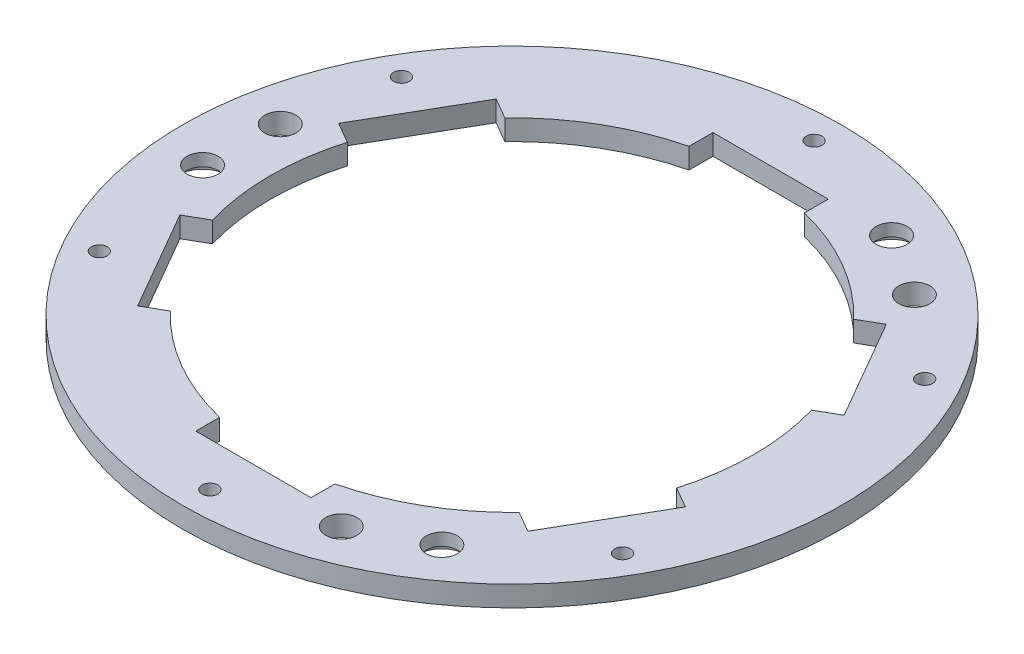
SolidWorks part; units mm, degrees
material "6061 Alloy"
ref_plane "Front Plane" through (0, 0, 0) normal (0, 0, 1) x (1, 0, 0)
ref_plane "Top Plane" through (0, 0, 0) normal (0, 1, 0) x (1, 0, 0)
ref_plane "Right Plane" through (0, 0, 0) normal (1, 0, 0) x (0, 0, -1)
sketch "Sketch1" plane through (0, 0, 0) normal (0, 1, 0) x (1, 0, 0)
  line L0 (-13.335, -54.2656) -> (-13.335, -58.1814)
  line L1 (13.335, -54.2656) -> (13.335, -58.1814)
  line L2 (-13.335, -59.7901) -> (13.335, -59.7901)
  line L3 (13.335, -58.1814) -> (13.335, -59.7901)
  line L4 (-13.335, -58.1814) -> (-13.335, -59.7901)
  line L5 (0, 0) -> (-65.7887, -5.7558) construction
  line L6 (0, 0) -> (0, -23.1086) construction
  line L7 (0, 0) -> (17.8146, -65.9496) construction
  line L8 (0, 0) -> (27.4515, -55.5868) construction
  line L9 (-65.0367, 11.4677) -> (0, 0) construction
  circle A0 centre (0, 0) radius 55.88
  circle A1 centre (0, 0) radius 76.2
  circle A2 centre (0, 0) radius 59.69
  circle A3 centre (0, -69.85) radius 1.8288
  circle A4 centre (-65.7887, -5.7558) radius 3.5941
  circle A5 centre (-65.0367, 11.4677) radius 3.5941
  circle A6 centre (42.4497, 50.5896) radius 3.5941
  circle A7 centre (22.587, -62.0573) radius 3.5941
  point P24 (0, 0)
  point P29 (0, 0)
  dimension "D1" = 111.76
  dimension "D2" = 152.4
  dimension "D8" = 3.6576
  dimension "D11" = 7.1882
  dimension "D4" = 13.335
  dimension "D5" = 13.335
  dimension "D7" = 69.85
  dimension "D6" = 5.5245
  dimension "D9" = 66.04
  dimension "D10" = 85
  dimension "D13" = 17.8146
  dimension "D14" = 68.3133
  dimension "D16" = 61.9958
  dimension "D17" = 14.1512
  dimension "D15" = 15
  dimension "D3" = 3.81
  dimension "D12" = 2
  dimension "D18" = 3
extrude "Boss-Extrude1" add sketch "Sketch1" along normal blind 4.7625 contours L1 A2 L0 A0 | A1 A2 A0 region at (-15.0127, 0, 56.2235) region at (-74.0447, 0, 0)
pattern_circular "CirPattern1" count 6 over 360 about axis through (0, 4.7625, 0) along (0, 1, 0) of face at (-13.335, 2.3813, 57.0278) of face at (13.335, 2.3813, 57.0278) of face at (0, 4.7625, 71.6788) of face at (0, 2.3813, 59.7901)
sketch "Sketch2" plane through (0, 0, 0) normal (1, 0, 0) x (0, 0, -1)
  line L0 (76.2, 4.7625) -> (-76.2, 4.7625) construction
  line L1 (-76.2, 0) -> (76.2, 0) construction
  line L2 (76.2, 4.7625) -> (-76.2, 4.7625)
  line L3 (-76.2, 0) -> (76.2, 0)
  line L4 (0, 0) -> (0, 4.7625) construction
  circle A0 centre (-75.2856, 0) radius 2.667
  dimension "D1" = 5.334
  dimension "D2" = 0.9144
revolve "Cut-Revolve1" [suppressed] cut sketch "Sketch2" angle 360 about L4
sketch "Sketch4" plane through (0, 0, 0) normal (0, -1, 0) x (1, 0, 0)
  line L0 (0, 0) -> (-65.7887, 5.7558) construction
  line L1 (0, 0) -> (0, -39.7137) construction
  circle A0 centre (-65.7887, 5.7558) radius 5.588
  circle A2 centre (-65.7887, 5.7558) radius 3.5941 construction
  circle A3 centre (-65.7887, 5.7558) radius 3.5941
  point P12 (0, 0)
  dimension "D2" = 11.176
extrude "Cut-Extrude1" cut sketch "Sketch4" against normal blind 1.905 contours A0 region at (-71.2186, 0, 5.7558)
pattern_circular "CirPattern2" count 3 over 360 about axis through (0, 0, 0) along (0, 1, 0) of face at (-65.7887, 4.7625, 9.3499) of face at (-65.7887, 1.905, 2.1617) of face at (-65.7887, 1.905, 0.1678)
sketch "Sketch5" plane through (0, 4.7625, 0) normal (0, 1, 0) x (1, 0, 0)
  line L0 (0, 0) -> (-20.0894, -55.1952)
  line L1 (0, 0) -> (0, -18.6852)
  line L2 (-16.5968, -53.0258) -> (-18.2257, -57.5011) construction
  line L3 (-18.2257, -57.5011) -> (-22.9993, -55.7636) construction
  line L4 (-22.9993, -55.7636) -> (-21.3704, -51.2884) construction
  line L5 (-59.7924, -7.9638) -> (-55.1022, -7.1368)
  line L6 (-54.2201, -12.1397) -> (-58.9103, -12.9667)
  line L7 (-58.9103, -12.9667) -> (-59.7924, -7.9638)
  line L8 (-36.7931, 47.7998) -> (-33.7318, 44.1515)
  line L9 (-37.6233, 40.8862) -> (-40.6846, 44.5345)
  line L10 (-40.6846, 44.5345) -> (-36.7931, 47.7998)
  line L11 (22.9993, 55.7636) -> (21.3704, 51.2884)
  line L12 (16.5968, 53.0258) -> (18.2257, 57.5011)
  line L13 (18.2257, 57.5011) -> (22.9993, 55.7636)
  line L14 (59.7924, 7.9638) -> (55.1022, 7.1368)
  line L15 (54.2201, 12.1397) -> (58.9103, 12.9667)
  line L16 (58.9103, 12.9667) -> (59.7924, 7.9638)
  line L17 (36.7931, -47.7998) -> (33.7318, -44.1515)
  line L18 (37.6233, -40.8862) -> (40.6846, -44.5345)
  line L19 (40.6846, -44.5345) -> (36.7931, -47.7998)
  circle A0 centre (0, 0) radius 55.5625
  circle A1 centre (0, 0) radius 58.7375 construction
  circle A2 centre (0, 0) radius 55.5625
  circle A3 centre (0, 0) radius 55.5625
  circle A4 centre (0, 0) radius 55.5625
  circle A5 centre (0, 0) radius 55.5625
  circle A6 centre (0, 0) radius 55.5625
  circle A7 centre (0, 0) radius 76.2
  circle A8 centre (0, 0) radius 63.5
  point P38 (0, 0)
  dimension "D1" = 111.125
  dimension "D3" = 20
  dimension "D4" = 2.54
  dimension "D5" = 4.7625
  dimension "D6" = 2.54
  dimension "D2" = 3.175
  dimension "D8" = 12.7
  dimension "D7" = 6
split line "Split Line1" [suppressed]
equation "\"Middle Coupler Inner Daimeter\"= 3.875in"
equation "\"Middle Coupler  Wall Thickness\" = 0.25in"
equation "\"Middle Coupler Bottom Thickness\"= 0.2in"
equation "\"Bearing Rail Offset\"= 0.45in"
equation "\"3-56 UNF Tap\"= 0.089in"
equation "\"3-56 UNF Clearance\"= 0.104in"
equation "\"Ball Bearing Distance\"= 0.03in"
equation "\"D1@Sketch1\"=\"Middle Coupler Inner Daimeter\"+0.5+0.0125*2in"
equation "\"TCA Outer Diameter\" = 6in"
equation "\"D2@Sketch1\"=\"TCA Outer Diameter\""
equation "\"D4@Sketch1\"=0.50 + (0.05/2)"
equation "\"D5@Sketch1\"=\"D4@Sketch1\""
equation "\"D7@Sketch1\"=(\"D2@Sketch1\"-0.5)/2"
equation "\"D8@Sketch1\"=\"6-32 Clearance\""
equation "\"D2@Sketch2\"=\"Interstage Aeroframe Wall Thickness\"/2"
equation "\"Interstage Aeroframe Wall Thickness\" = 0.072in"
equation "\"Compression Spring OD\"= 0.42in"
equation "\"10-24 Tap\"= 0.157in"
equation "\"10-24 Clearance\"= 0.196in"
equation "\"D2@Sketch4\"=\"Compression Spring OD\"+0.02"
equation "\"D3@Sketch1\"=0.125in+(0.05/2)"
equation "\"Lower Stage Fuselage Wall Thickness\" = 0.25in"
equation "\"6-32 Tap\" = 0.107in"
equation "\"1/4-20 Tap\" = 0.201in"
equation "\"3-48 Tap\"= 0.079in"
equation "\"12-24 Tap\" = 0.177in"
equation "\"3-48 Clearance\" = 0.104in"
equation "\"6-32 Clearance\" = 0.144"
equation "\"D6@Sketch1\"=3/16 + 0.03"
equation "\"D9@Sketch1\"=(\"D2@Sketch1\"+\"D1@Sketch1\")/4+0.1-.1"
equation "\"D1@Sketch5\"=\"Middle Coupler Inner Daimeter\"+0.5"
equation "\"D5@Sketch5\"=3/16"
equation "\"D6@Sketch5\"=\"D4@Sketch5\""
equation "\"D1@Boss-Extrude1\"=3/16"
